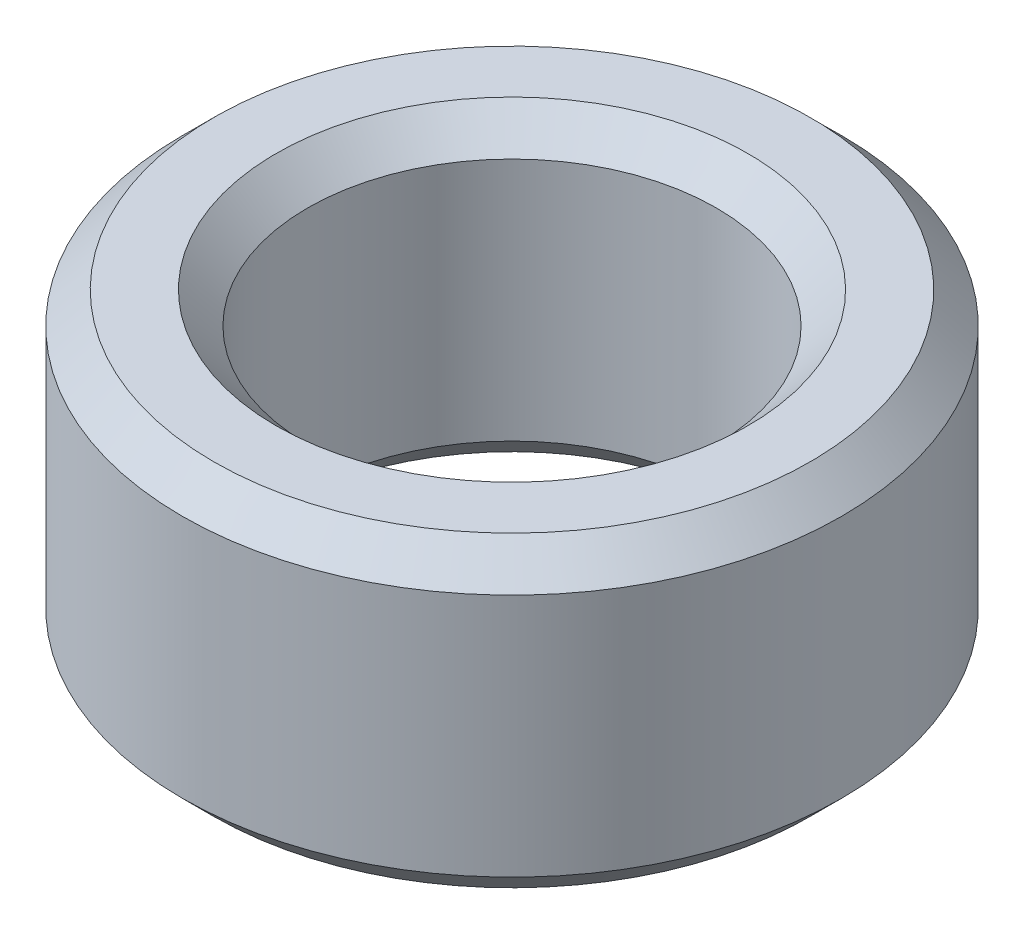
SolidWorks part; units mm, degrees
ref_plane "Front Plane" through (0, 0, 0) normal (0, 0, 1) x (1, 0, 0)
ref_plane "Top Plane" through (0, 0, 0) normal (0, 1, 0) x (1, 0, 0)
ref_plane "Right Plane" through (0, 0, 0) normal (1, 0, 0) x (0, 0, -1)
sketch "Sketch1" plane through (0, 0, 0) normal (0, 1, 0) x (1, 0, 0)
  circle A0 centre (0, 0) radius 37.5
  dimension "SLEEVE_OD" = 75
extrude "Boss-Extrude1" add sketch "Sketch1" along normal blind 34.9344
sketch "Sketch2" plane through (0, 0, 0) normal (0, 1, 0) x (1, 0, 0)
  circle A0 centre (0, 0) radius 23.2514
  dimension "BORE_D" = 46.5029
extrude "Cut-Extrude1" cut sketch "Sketch2" along normal through all
chamfer "Chamfer1" distance 3.578 angle 45 4 edges at (0, 34.9344, 23.2514) (0, 0, 23.2514) (0, 0, 37.5) (0, 34.9344, 37.5)
